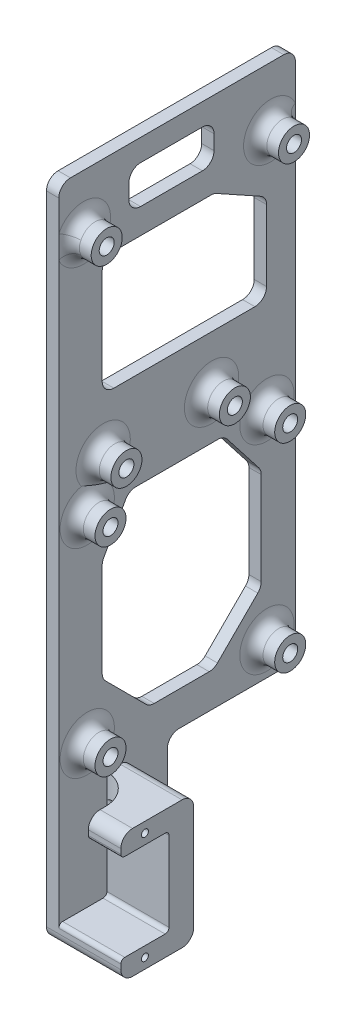
SolidWorks part; units mm, degrees
ref_plane "Front Plane" through (0, 0, 0) normal (0, 0, 1) x (1, 0, 0)
ref_plane "Top Plane" through (0, 0, 0) normal (0, 1, 0) x (1, 0, 0)
ref_plane "Right Plane" through (0, 0, 0) normal (1, 0, 0) x (0, 0, -1)
sketch "Sketch1" plane through (0, 0, 0) normal (1, 0, 0) x (0, 0, -1)
  line L1 (0, 0) -> (60.96, 0)
  line L2 (0, 0) -> (0, 170.18)
  line L3 (0, 170.18) -> (60.96, 170.18)
  line L4 (60.96, 0) -> (60.96, 170.18)
  dimension "D1" = 60.96
  dimension "D2" = 170.18
extrude "Boss-Extrude1" add sketch "Sketch1" along normal blind 3.175 contours L2 L3 L4 L1
ref_plane "Plane1" through (0, 0, -30.48) normal (0, 0, 1) x (1, 0, 0)
sketch "Sketch2" plane through (3.175, 0, 0) normal (1, 0, 0) x (0, 0, -1)
  circle A0 centre (6.35, 156.21) radius 4
  circle A1 centre (54.61, 154.94) radius 4
  circle A2 centre (11.43, 104.14) radius 4
  circle A3 centre (39.37, 104.14) radius 4
  circle A4 centre (7.33, 93.1) radius 4
  circle A5 centre (53.63, 93.1) radius 4
  circle A6 centre (7.33, 41.8) radius 4
  circle A7 centre (53.63, 41.8) radius 4
  point P0 (6.35, 156.21)
  point P1 (54.61, 154.94)
  point P3 (39.37, 104.14)
  point P5 (11.43, 104.14)
  dimension "D1" = 8
extrude "Boss-Extrude2" add sketch "Sketch2" along normal blind 6
hole_wizard "#24 (0.152) Diameter Hole1" positions "Sketch3" profile "Sketch4" hole size "#24" standard "ANSI Inch" end condition up to next
sketch "Sketch3" plane through (9.175, 0, 0) normal (1, 0, 0) x (0, 0, -1)
  point P0 (153.5671, 87.7333)
  point P2 (6.35, 156.21)
  point P5 (54.61, 154.94)
  point P8 (39.37, 104.14)
  point P11 (11.43, 104.14)
  point P14 (7.33, 93.1)
  point P17 (53.63, 93.1)
  point P20 (7.33, 41.8)
  point P23 (53.63, 41.8)
sketch "Sketch4" plane through (9.175, 87.7333, -153.5671) normal (0, 1, 0) x (0, 0, -1)
  line L0 (0, 0) -> (0, 9.175)
  line L1 (0, 9.175) -> (1.9304, 9.175)
  line L2 (1.9304, 9.175) -> (1.9304, 0)
  line L5 (1.9304, 0) -> (0, 0)
  line L11 (0, -6.35) -> (0, 107.95) construction
  dimension "Thru Hole Dia." = 3.8608
  dimension "Thru Hole Depth" = 9.175
sketch "Sketch6" plane through (3.175, 0, 0) normal (1, 0, 0) x (0, 0, -1)
  line L0 (0, 27.76) -> (0, 33.02)
  line L1 (0, 0) -> (18.75, 0)
  line L2 (0, 0) -> (0, 5.26)
  line L3 (0, 33.02) -> (18.75, 33.02)
  line L4 (18.75, 0) -> (18.75, 33.02)
  line L5 (0, 27.76) -> (12.4, 27.76)
  line L7 (0, 5.26) -> (12.4, 5.26)
  line L8 (12.4, 27.76) -> (12.4, 5.26)
  point P9 (12.4, 16.51)
  point P10 (18.75, 16.51)
  dimension "D1" = 22.5
  dimension "D2" = 33.02
  dimension "D3" = 6.35
  dimension "D4" = 12.4
extrude "Boss-Extrude3" add sketch "Sketch6" along normal blind 16
sketch "Sketch7" plane through (0, 33.02, 0) normal (0, 1, 0) x (1, 0, 0)
  line L0 (19.175, 12.4) -> (3.175, 12.4) construction
  line L1 (3.175, 0) -> (10.795, 0)
  line L2 (3.175, 0) -> (3.175, 12.4)
  line L3 (3.175, 12.4) -> (10.795, 12.4)
  line L4 (10.795, 0) -> (10.795, 12.4)
  dimension "D1" = 7.62
extrude "Cut-Extrude1" cut sketch "Sketch7" against normal up to surface (5.26 mm away) up to face at (11.175, 27.76, -6.2)
sketch "Sketch8" plane through (19.175, 0, 0) normal (1, 0, 0) x (0, 0, -1)
  line L0 (6.2, 30.3639) -> (6.2, 2.6561) construction
  line L1 (12.4, 27.76) -> (12.4, 5.26) construction
  line L2 (12.4, 27.76) -> (12.4, 5.26) construction
  line L3 (0, 27.76) -> (12.4, 27.76) construction
  line L4 (0, 27.76) -> (12.4, 27.76) construction
  circle A0 centre (6.2, 30.3639) radius 0.9
  circle A1 centre (6.2, 2.6561) radius 0.9
  point P6 (12.4, 16.51)
  point P7 (6.2, 16.51)
  point P10 (6.2, 27.76)
  dimension "D1" = 1.8
extrude "Cut-Extrude2" cut sketch "Sketch8" against normal up to next
sketch "Sketch9" plane through (3.175, 0, 0) normal (1, 0, 0) x (0, 0, -1)
  line L0 (11.1859, 148.2342) -> (11.1859, 117.6644)
  line L1 (11.1859, 117.6644) -> (53.5327, 117.6644)
  line L2 (53.5327, 117.6644) -> (53.5327, 140.7171)
  line L3 (53.5327, 140.7171) -> (40.0018, 148.2342)
  line L4 (40.0018, 148.2342) -> (11.1859, 148.2342)
  line L5 (18.0696, 92.8199) -> (11.1859, 80.4294)
  line L6 (11.1859, 80.4294) -> (11.1859, 54.2696)
  line L7 (11.1859, 54.2696) -> (23.3387, 42.1168)
  line L8 (23.3387, 42.1168) -> (40.0018, 42.1168)
  line L9 (40.0018, 42.1168) -> (52.1545, 54.2696)
  line L10 (52.1545, 54.2696) -> (52.1545, 80.4294)
  line L11 (52.1545, 80.4294) -> (42.5075, 92.8199)
  line L12 (42.5075, 92.8199) -> (18.0696, 92.8199)
  line L13 (60.96, 33.3113) -> (27.9743, 33.3113)
  line L14 (60.96, 0) -> (60.96, 170.18) construction
  line L15 (27.9743, 33.3113) -> (27.9743, 0)
  line L16 (18.75, 0) -> (60.96, 0) construction
  line L17 (27.9743, 0) -> (60.96, 0)
  line L18 (60.96, 0) -> (60.96, 33.3113)
  line L19 (18.0696, 164.5214) -> (18.0696, 154.7491)
  line L20 (18.0696, 154.7491) -> (40.0018, 154.7491)
  line L21 (40.0018, 154.7491) -> (40.0018, 164.5214)
  line L22 (40.0018, 164.5214) -> (18.0696, 164.5214)
extrude "Cut-Extrude3" cut sketch "Sketch9" against normal up to next
fillet "Fillet1" radius 3 8 edges at (3.175, 41.8, -57.63) (3.175, 41.8, -11.33) (3.175, 93.1, -57.63) (3.175, 93.1, -11.33) (3.175, 104.14, -43.37) (3.175, 104.14, -15.43) (3.175, 154.94, -58.61) (3.175, 156.21, -10.35)
fillet "Fillet3" radius 3 26 edges at (9.5875, 0, 0) (1.5875, 170.18, 0) (1.5875, 170.18, -60.96) (1.5875, 33.3113, -60.96) (1.5875, 0, -27.9743) (1.5875, 33.3113, -27.9743) (1.5875, 140.7171, -53.5327) (1.5875, 117.6644, -53.5327) (1.5875, 117.6644, -11.1859) (1.5875, 148.2342, -40.0018) (1.5875, 80.4294, -52.1545) (1.5875, 54.2696, -52.1545) (1.5875, 42.1168, -40.0018) (1.5875, 42.1168, -23.3387) (1.5875, 54.2696, -11.1859) (1.5875, 80.4294, -11.1859) (1.5875, 92.8199, -18.0696) (1.5875, 92.8199, -42.5075) (1.5875, 154.7491, -40.0018) (1.5875, 154.7491, -18.0696) (1.5875, 164.5214, -18.0696) (1.5875, 164.5214, -40.0018) (1.5875, 148.2342, -11.1859) (14.985, 33.02, 0) (11.175, 33.02, -18.75) (11.175, 0, -18.75)
fillet "Fillet4" radius 8 1 edges at (10.795, 30.39, -12.4)
fillet "Fillet5" radius 1 4 edges at (14.985, 27.76, 0) (11.175, 27.76, -12.4) (11.175, 5.26, 0) (11.175, 5.26, -12.4)
